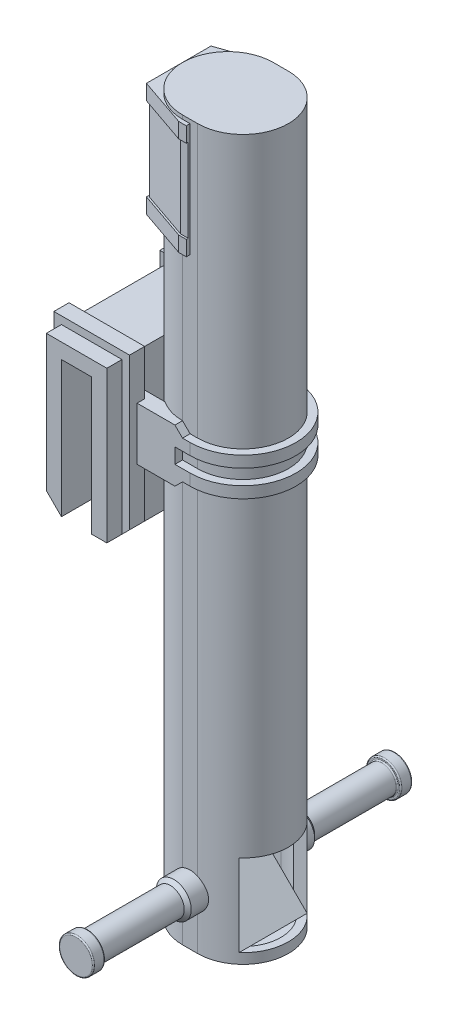
SolidWorks part; units mm, degrees
ref_plane "Front Plane" through (0, 0, 0) normal (0, 0, 1) x (1, 0, 0)
ref_plane "Top Plane" through (0, 0, 0) normal (0, 1, 0) x (1, 0, 0)
ref_plane "Right Plane" through (0, 0, 0) normal (1, 0, 0) x (0, 0, -1)
sketch "Sketch1" plane through (0, 0, 0) normal (0, 0, 1) x (1, 0, 0)
  line L0 (-51.9447, -77.5874) -> (-61.9447, -67.5874)
  line L1 (-51.9447, 12.4126) -> (-31.9447, 12.4126)
  line L2 (-51.9447, 12.4126) -> (-51.9447, -77.5874)
  line L4 (-31.9447, 12.4126) -> (-31.9447, -77.5874)
  line L5 (-61.9447, -67.5874) -> (-61.9447, 22.4126)
  line L6 (-61.9447, 22.4126) -> (-21.9447, 22.4126)
  line L7 (-21.9447, 22.4126) -> (-21.9447, -77.5874)
  line L8 (-21.9447, -77.5874) -> (-31.9447, -77.5874)
  line L9 (-21.9447, 9.0563) -> (-31.9447, 9.0563) construction
  line L10 (-42.9825, 22.4126) -> (-42.9825, 12.4126) construction
  line L11 (-61.9447, 9.0563) -> (-51.9447, 9.0563) construction
  dimension "D1" = 40
  dimension "D2" = 90
  dimension "D3" = 45
  dimension "D4" = 10
extrude "Boss-Extrude1" add sketch "Sketch1" along normal blind 100
sketch "Sketch3" plane through (0, 0, 100) normal (0, 0, 1) x (1, 0, 0)
  line L0 (-61.9447, -67.5874) -> (-66.9447, -67.5874)
  line L1 (-41.2735, 22.4126) -> (-41.2735, 27.4126)
  line L2 (-21.9447, 22.4126) -> (-61.9447, 22.4126) construction
  line L3 (-21.9447, -33.0039) -> (-16.9447, -33.0039)
  line L4 (-21.9447, -77.5874) -> (-21.9447, 22.4126) construction
  line L5 (-66.9447, -67.5874) -> (-66.9447, 27.4126)
  line L6 (-66.9447, 27.4126) -> (-16.9447, 27.4126)
  line L7 (-16.9447, 27.4126) -> (-16.9447, -72.5874)
  line L8 (-16.9447, -72.5874) -> (-21.9447, -77.5874)
  line L9 (-21.9447, -77.5874) -> (-21.9447, 22.4126)
  line L10 (-21.9447, 22.4126) -> (-61.9447, 22.4126)
  line L11 (-61.9447, 22.4126) -> (-61.9447, -67.5874)
  line M8 (-21.9447, -77.5874) -> (-21.9447, 22.4126)
  line M9 (-21.9447, 22.4126) -> (-61.9447, 22.4126)
  line M10 (-61.9447, 22.4126) -> (-61.9447, -67.5874)
  dimension "D1" = 5
extrude "Boss-Extrude2" add sketch "Sketch3" against normal blind 10 from offset 10 contours L6 L5 L0 L1 M10 M9 | L7 L6 L1 L3 M9 M8 | L8 L7 L3 M8 region at (-62.1509, -12.0456, 100) region at (-40.6222, 24.9126, 100) region at (-19.4942, -54.0704, 100) offset against normal yes
ref_plane "Plane1" through (0, 0, 50) normal (0, 0, -1) x (-1, 0, 0)
mirror "Mirror1" about plane through (0, 0, 50) normal (0, 0, -1) of "Boss-Extrude2"
sketch "Sketch4" plane through (-21.9447, 0, 0) normal (1, 0, 0) x (0, 0, -1)
  line L0 (-85, 30.3631) -> (-85, -69.6369) construction
  line L1 (-50, -22) -> (-50, 22) construction
  line L2 (-15, -37.5874) -> (-25, -37.5874)
  line L3 (-77.6412, -2.5874) -> (-77.6412, 22.4126) construction
  line L4 (-25, -2.5874) -> (-25, -37.5874)
  line L5 (-15, -72.5874) -> (-15, 27.4126) construction
  line L6 (-15, -2.5874) -> (-25, -2.5874)
  line L7 (-85, -2.5874) -> (-75, -2.5874)
  line L8 (-85, -2.5874) -> (-85, -37.5874)
  line L9 (-85, -37.5874) -> (-75, -37.5874)
  line L10 (-75, -2.5874) -> (-75, -37.5874)
  line L11 (-80, 22.4126) -> (-20, 22.4126) construction
  line L12 (-15, -2.5874) -> (-15, -37.5874)
  dimension "D1" = 25
  dimension "D2" = 35
  dimension "D3" = 10
  dimension "D4" = 25
extrude "Boss-Extrude3" add sketch "Sketch4" along normal blind 30
sketch "Sketch7" plane through (0, -2.5874, 0) normal (0, 1, 0) x (1, 0, 0)
  line L1 (8.0553, -15) -> (8.0553, -25) construction
  line L2 (8.0553, -75) -> (8.0553, -85) construction
  line L3 (8.0553, -20) -> (18.0553, -20)
  line L4 (8.0553, -80) -> (18.0553, -80)
  line L5 (-21.9447, -40.6008) -> (-21.9447, -59.3992)
  line L6 (-21.9447, -59.3992) -> (-20.4342, -59.3992)
  line L8 (-21.9447, -40.6008) -> (-20.4342, -40.6008)
  line L9 (-20.4342, -59.3992) -> (-20.4342, -40.6008)
  arc A0 (8.0553, -20) -> (8.0553, -80) centre (8.0553, -50) ccw
  arc A1 (18.0553, -80) -> (18.0553, -20) centre (18.0553, -50) ccw
  point P11 (-21.9447, -50)
  line M4 (8.0553, -85) -> (8.0553, -75)
  line M5 (8.0553, -75) -> (-21.9447, -75)
extrude "Boss-Extrude6" add sketch "Sketch7" along normal up to surface and the other way up to surface contours A0 L5 L6 | A0 L8 L5 | A0 L9 region at (-21.4936, -2.5874, 42.9386) region at (-21.0397, -2.5874, 50) region at (-21.4936, -2.5874, 57.0614) up to face at (-41.9447, 22.4126, 50) other way up to face at (-24.4447, -77.5874, 50)
extrude "Boss-Extrude7" add sketch "Sketch7<3>" along normal blind 175 and the other way blind 300 contours L4 A1 L3 A0 L9 M5 M4 | A0 M5 M4 | A0 L9 region at (13.4384, -2.5874, 49.5465) region at (-21.0397, -2.5874, 50) region at (1.7612, -2.5874, 77.015)
sketch "Sketch7<3>" plane through (0, -2.5874, 0) normal (0, 1, 0) x (1, 0, 0) same geometry as "Sketch7"
sketch "Sketch8" plane through (0, -2.5874, 0) normal (0, 1, 0) x (1, 0, 0)
  line L0 (18.0553, -85) -> (18.0553, -15) construction
  line L1 (18.0553, -85) -> (8.0553, -85)
  line L2 (8.0553, -85) -> (8.0553, -80)
  line L3 (8.0553, -80) -> (18.0553, -80)
  line L4 (18.0553, -15) -> (8.0553, -15)
  line L5 (8.0553, -15) -> (8.0553, -20)
  line L6 (8.0553, -20) -> (18.0553, -20)
  arc A0 (18.0553, -85) -> (18.0553, -15) centre (18.0553, -50) ccw
  arc A1 (18.0553, -80) -> (18.0553, -20) centre (18.0553, -50) ccw
extrude "Boss-Extrude8" add sketch "Sketch8" against normal blind 25 from offset 5 offset against normal yes
chamfer "Chamfer2" distance 5 angle 45 4 edges at (8.0553, -7.5874, 17.5) (8.0553, -32.5874, 17.5) (8.0553, -32.5874, 82.5) (8.0553, -7.5874, 82.5)
extrude "Cut-Extrude1" cut sketch "Sketch8<2>" against normal mid plane 10 from offset 17.5 offset against normal yes
sketch "Sketch8<2>" plane through (0, -2.5874, 0) normal (0, 1, 0) x (1, 0, 0) same geometry as "Sketch8"
sketch "Sketch9" plane through (0, 172.4126, 0) normal (0, 1, 0) x (1, 0, 0)
  line L0 (8.0553, -20) -> (-21.9447, -30.3004)
  line L1 (-21.9447, -40.6008) -> (-21.9447, -20) construction
  line L2 (-21.9447, -30.3004) -> (-21.9447, -69.6996)
  line L3 (-21.9447, -80) -> (-21.9447, -59.3992) construction
  line L4 (-21.9447, -69.6996) -> (8.0553, -80)
  line L5 (8.0553, -80) -> (8.0553, -20)
  line L6 (8.0553, -50) -> (-21.9447, -50) construction
  line L7 (-21.9447, -40.6008) -> (-20.4342, -40.6008)
  line L8 (8.0553, -15) -> (8.0553, -20) construction
  line L9 (-21.9447, -59.3992) -> (-20.4342, -59.3992)
  line L10 (8.0553, -80) -> (8.0553, -85) construction
  line L11 (-21.9447, -69.6996) -> (-21.9447, -72.1996)
  line L12 (-21.9447, -30.3004) -> (-21.9447, -27.8004)
  line L14 (-24.4447, -28.6588) -> (-24.4447, -71.3412)
  line L15 (8.0553, -17.5) -> (-24.4447, -28.6588)
  line L16 (8.0553, -82.5) -> (-24.4447, -71.3412)
  line L17 (8.0553, -82.5) -> (13.0553, -82.5)
  line L18 (13.0553, -80) -> (13.0553, -85) construction
  line L19 (13.0553, -82.5) -> (13.0553, -80)
  line L20 (8.0553, -80) -> (18.0553, -80) construction
  line L21 (13.0553, -80) -> (8.0553, -80)
  line L22 (8.0553, -20) -> (13.0553, -20)
  line L23 (8.0553, -20) -> (18.0553, -20) construction
  line L24 (13.0553, -20) -> (13.0553, -17.5)
  line L25 (13.0553, -15) -> (13.0553, -20) construction
  line L26 (13.0553, -17.5) -> (8.0553, -17.5)
  arc A1 (-20.4342, -40.6008) -> (-20.4342, -59.3992) centre (8.0553, -50) ccw
  arc M12 (8.0553, -20) -> (8.0553, -80) centre (8.0553, -50) ccw
  line M13 (8.0553, -80) -> (18.0553, -80)
  line M15 (18.0553, -20) -> (8.0553, -20)
extrude "Boss-Extrude11" add sketch "Sketch9" against normal blind 75 from offset 2.5 contours L16 L11 L2 L12 L15 L14 | L7 L2 M12 | L2 L9 M12 | L24 L26 L15 L12 L0 M12 M15 | L17 L19 L4 L11 L16 M13 M12 | L4 M12 | L2 L7 L0 M12 | L9 L2 L4 M12 region at (-1.8078, 172.4126, 21.2734) region at (-18.6106, 172.4126, 32.8725) region at (-1.3705, 172.4126, 77.4529) region at (10.5553, 172.4126, 80.3727) region at (-23.1864, 172.4126, 50) region at (-21.4936, 172.4126, 42.9386) region at (-18.6106, 172.4126, 67.1275) region at (-21.4936, 172.4126, 57.0614) offset against normal yes
ref_plane "Plane2" through (0, 132.4126, 0) normal (0, 1, 0) x (1, 0, 0)
extrude "Cut-Extrude3" cut sketch "Sketch9<4>" against normal mid plane 55 from surface contours L24 L26 L15 L12 L0 M12 M15 | L16 L11 L2 L12 L15 L14 | L2 L7 L0 M12 | L2 L9 M12 | L7 L2 M12 | L9 L2 L4 M12 | L17 L19 L4 L11 L16 M13 M12 | L0 M12 | L4 M12 region at (-1.8078, 172.4126, 21.2734) region at (-1.3705, 172.4126, 22.5471) region at (-18.6106, 172.4126, 32.8725) region at (-1.3705, 172.4126, 77.4529) region at (10.5553, 172.4126, 80.3727) region at (-23.1864, 172.4126, 50) region at (-21.4936, 172.4126, 42.9386) region at (-18.6106, 172.4126, 67.1275) region at (-21.4936, 172.4126, 57.0614) starting at plane "Plane2"
sketch "Sketch9<4>" plane through (0, 172.4126, 0) normal (0, 1, 0) x (1, 0, 0) same geometry as "Sketch9"
sketch "Sketch10" plane through (0, 104.9126, 0) normal (0, 1, 0) x (1, 0, 0)
  line L0 (8.0553, -17.5) -> (8.0553, -20)
  line L1 (8.0553, -15) -> (8.0553, -20) construction
  line L2 (-24.4447, -33.0369) -> (-23.1947, -33.0369)
  line L3 (-24.4447, -28.6588) -> (-24.4447, -71.3412) construction
  line L4 (8.0553, -80) -> (8.0553, -82.5)
  line L5 (8.0553, -81.25) -> (13.0553, -81.25)
  line L6 (13.0553, -82.5) -> (13.0553, -80) construction
  line L7 (13.0553, -81.25) -> (13.0553, -18.75)
  line L8 (13.0553, -20) -> (13.0553, -17.5) construction
  line L9 (13.0553, -18.75) -> (8.0553, -18.75)
  line L10 (8.0553, -18.75) -> (-23.1947, -29.4796)
  line L11 (-23.1947, -29.4796) -> (-23.1947, -70.5204)
  line L12 (-23.1947, -70.5204) -> (8.0553, -81.25)
  line L13 (8.0553, -82.5) -> (-24.4447, -71.3412) construction
  line L14 (8.0553, -17.5) -> (-24.4447, -28.6588) construction
  line M5 (13.0553, -82.5) -> (13.0553, -80)
  line M6 (13.0553, -80) -> (8.0553, -80)
  line M7 (8.0553, -80) -> (-10.373, -73.6727)
  arc M8 (-10.373, -73.6727) -> (-10.373, -26.3273) centre (8.0553, -50) cw
  line M9 (-10.373, -26.3273) -> (8.0553, -20)
  line M10 (8.0553, -20) -> (13.0553, -20)
  line M11 (13.0553, -20) -> (13.0553, -17.5)
extrude "Boss-Extrude12" add sketch "Sketch10" along normal up to surface (55 mm away) contours L11 L12 L4 L0 L10 M7 M8 M9 | L7 M6 M10 M9 M8 M7 | L9 L0 M11 M10 | L4 L5 M5 M6 region at (10.5553, 104.9126, 19.375) region at (7.3566, 104.9126, 19.375) region at (-2.0268, 104.9126, 50) region at (10.5553, 104.9126, 80.625) up to face at (0.2696, 159.9126, 50)
sketch "Sketch11" plane through (0, 172.4126, 0) normal (0, 1, 0) x (1, 0, 0)
  line L0 (8.0553, -25) -> (18.0553, -25)
  line L1 (18.0553, -75) -> (8.0553, -75)
  line L2 (18.0553, -80) -> (18.0553, -20) construction
  line L4 (18.0553, -80) -> (13.0553, -80) construction
  line L6 (8.0553, -20) -> (18.0553, -20) construction
  line L7 (8.0553, -80) -> (8.0553, -20) construction
  line L8 (12.3298, -25) -> (12.3298, -20) construction
  arc A0 (18.0553, -75) -> (18.0553, -25) centre (18.0553, -50) ccw
  arc A1 (8.0553, -25) -> (8.0553, -75) centre (8.0553, -50) ccw
  arc A2 (18.0553, -80) -> (18.0553, -20) centre (18.0553, -50) ccw construction
  arc A3 (18.0553, -80) -> (18.0553, -20) centre (18.0553, -50) ccw construction
  point P15 (18.0553, -50)
extrude "Cut-Extrude4" cut sketch "Sketch11" against normal blind 465 from offset 5 contours A1 L1 A0 L0 offset against normal yes
sketch "Sketch13" plane through (-21.9447, 0, 0) normal (1, 0, 0) x (0, 0, -1)
  line L0 (-50, -302.5874) -> (-50, -234.9479)
  line L1 (-80, -302.5874) -> (-20, -302.5874) construction
  line L3 (-72.5, -241.6785) -> (-27.5, -241.6785)
  line L4 (-72.5, -241.6785) -> (-72.5, -295.8568)
  line L5 (-72.5, -295.8568) -> (-27.5, -295.8568)
  line L6 (-27.5, -241.6785) -> (-27.5, -295.8568)
  line L7 (-72.5, -241.6785) -> (-27.5, -295.8568) construction
  line L8 (-72.5, -295.8568) -> (-27.5, -241.6785) construction
  point P4 (-50, -268.7676)
extrude "Cut-Extrude6" cut sketch "Sketch13" against normal blind 39 from offset 80 contours L4 L5 L0 L3 | L6 L3 L0 L5 region at (-21.9447, -268.7676, 61.25) region at (-21.9447, -268.7676, 38.75)
sketch "Sketch15" plane through (0, 0, 27.5) normal (0, 0, 1) x (1, 0, 0)
  line L0 (37.8985, -295.8568) -> (-16.9447, -241.0137)
  line L1 (-16.9447, 167.4126) -> (-16.9447, -297.5874) construction
  line L2 (-16.9447, -241.0137) -> (-16.9447, -246.8949)
  line L3 (-16.9447, -246.8949) -> (32.0172, -295.8568)
  line L4 (28.9526, -295.8568) -> (37.8985, -295.8568) construction
  line L5 (32.0172, -295.8568) -> (37.8985, -295.8568)
extrude "Boss-Extrude13" add sketch "Sketch15" along normal up to surface (45 mm away) contours L0 L2 L3 L5 up to face at (33.4255, -268.7676, 72.5)
sketch "Sketch16" plane through (0, -302.5874, 0) normal (0, -1, 0) x (1, 0, 0)
  line L0 (-16.9447, 72.5) -> (-16.9447, 66.5831)
  line L1 (-16.9447, 72.5) -> (-11.7878, 72.5)
  line L2 (-16.9447, 72.5) -> (-11.7878, 72.5) construction
  line L3 (-16.9447, 27.5) -> (-16.9447, 33.4169)
  line L4 (-16.9447, 27.5) -> (-11.7878, 27.5)
  arc A0 (-11.7878, 72.5) -> (-16.9447, 66.5831) centre (8.0553, 50) ccw
  arc A1 (-16.9447, 33.4169) -> (-11.7878, 27.5) centre (8.0553, 50) ccw
extrude "Cut-Extrude7" cut sketch "Sketch16" against normal blind 72
scale "Scale1" scale about centroid uniform scaling yes scale factor 1.3
sketch "Sketch17" plane through (0, 0, 11) normal (0, 0, -1) x (-1, 0, 0)
  line L2 (-25.1233, -379.9733) -> (-25.1233, -28.9733) construction
  line L3 (-25.1233, -336.0076) -> (-12.1233, -336.0076)
  line L4 (-12.1233, -379.9733) -> (-12.1233, -35.4733) construction
  circle A0 centre (-18.6233, -336.0076) radius 15
  line M1 (-12.1233, -379.9733) -> (-12.1233, -35.4733)
  line M4 (-25.1233, -28.9733) -> (-25.1233, -379.9733)
extrude "Boss-Extrude14" add sketch "Sketch17" along normal blind 100 and the other way blind 0.0001 from offset 2 contours A0 L3 M4 M1 | A0 M4 | A0 L3 M1 M4 | A0 M1 region at (18.6233, -328.7428, 11) region at (28.6224, -336.0076, 11) region at (18.6233, -343.2724, 11) region at (8.6243, -336.0076, 11) offset against normal yes
sketch "Sketch19" plane through (0, 0, -87) normal (0, 0, -1) x (-1, 0, 0)
  circle A0 centre (-18.6233, -336.0076) radius 15
  circle A1 centre (-18.6233, -336.0076) radius 12
extrude "Cut-Extrude8" cut sketch "Sketch19" against normal blind 70 from offset 10 offset against normal yes
chamfer "Chamfer3" distance 4 angle 45 1 edges at (3.6233, -336.0076, -7)
fillet "Fillet1" radius 1 3 edges at (3.6233, -336.0076, -87) (3.6233, -336.0076, -77) (6.6233, -336.0076, -77)
ref_plane "Plane3" through (0, 0, 50) normal (0, 0, -1) x (-1, 0, 0)
mirror "Mirror9" about plane through (0, 0, 50) normal (0, 0, -1) of "Fillet1", "Chamfer3", "Cut-Extrude8", "Boss-Extrude14"
